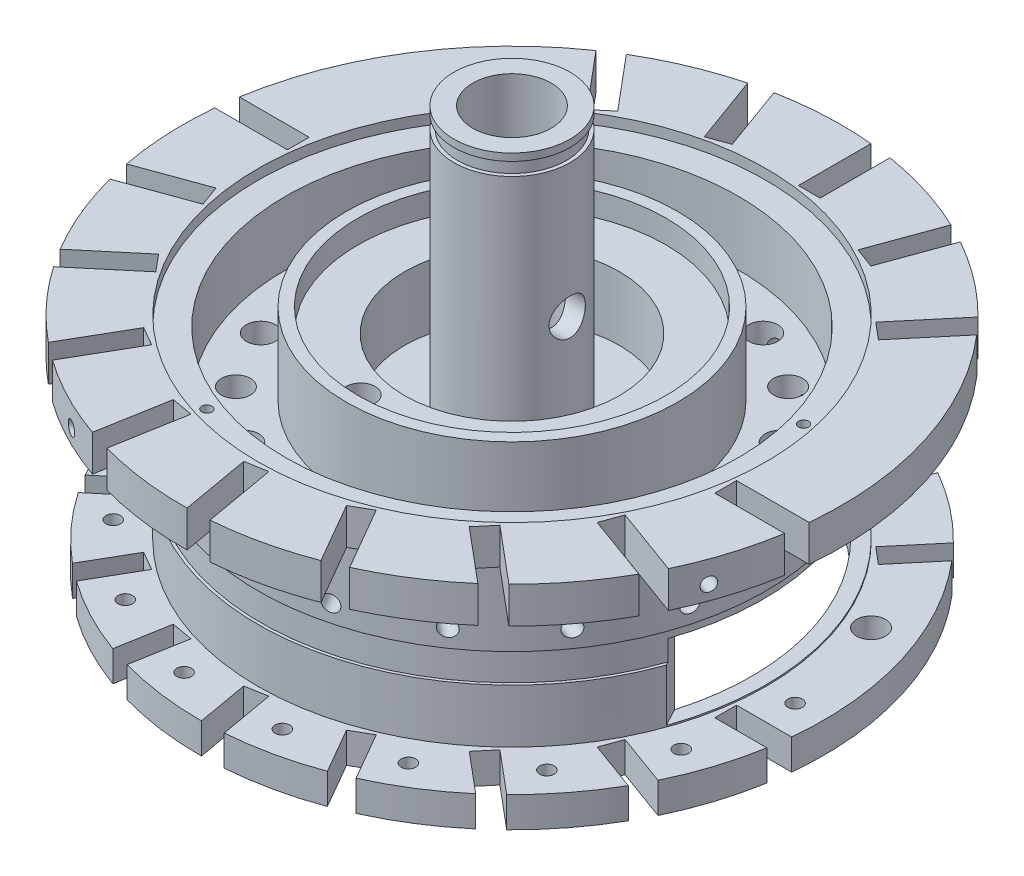
SolidWorks part; units mm, degrees
note: The reader was unsure of these and kept them because the rebuilt part matched: shared geometry of "Sketch13<3>".
ref_plane "Front Plane" through (0, 0, 0) normal (0, 0, 1) x (1, 0, 0)
ref_plane "Top Plane" through (0, 0, 0) normal (0, 1, 0) x (1, 0, 0)
ref_plane "Right Plane" through (0, 0, 0) normal (1, 0, 0) x (0, 0, -1)
sketch "Sketch1" plane through (0, 0, 0) normal (0, 1, 0) x (1, 0, 0)
  circle A0 centre (0, 0) radius 21.5
  dimension "D1" = 43
extrude "Boss-Extrude1" add sketch "Sketch1" along normal blind 2.1
sketch "Sketch2" plane through (0, 2.1, 0) normal (0, 1, 0) x (1, 0, 0)
  circle A0 centre (0, 0) radius 17.5
  dimension "D1" = 35
extrude "Boss-Extrude2" add sketch "Sketch2" along normal blind 10.9
sketch "Sketch3" plane through (0, 13, 0) normal (0, 1, 0) x (1, 0, 0)
  circle A0 centre (0, 0) radius 22.7
  dimension "D1" = 45.4
extrude "Boss-Extrude3" add sketch "Sketch3" along normal blind 2.5
sketch "Sketch4" plane through (0, 0, 0) normal (0, 0, 1) x (1, 0, 0)
  line L0 (0, 0) -> (0, 15.5) construction
  line L1 (22.7, 15.5) -> (-22.7, 15.5) construction
  line L2 (-16.5, 7.6) -> (-16.5, 0)
  line L3 (-21.5, 0) -> (21.5, 0) construction
  line L4 (-16.5, 7.6) -> (-6.5, 7.6)
  line L5 (-6.5, 7.6) -> (-6.5, 7.4)
  line L6 (-6.5, 7.4) -> (-4.5, 7.4)
  line L7 (-4.5, 7.4) -> (-4.5, 8.4)
  line L8 (-4.5, 8.4) -> (0, 8.4)
  line L9 (0, 8.4) -> (0, 0)
  line L10 (0, 0) -> (-16.5, 0)
  dimension "D1" = 33
  dimension "D2" = 9
  dimension "D3" = 7.4
  dimension "D4" = 13
  dimension "D5" = 0.2
  dimension "D6" = 1
revolve "Cut-Revolve1" cut sketch "Sketch4" angle 360 about L0
sketch "Sketch5" plane through (0, 15.5, 0) normal (0, 1, 0) x (1, 0, 0)
  circle A0 centre (0, 0) radius 11.4
  dimension "D1" = 22.8
extrude "Boss-Extrude4" add sketch "Sketch5" along normal blind 0.5
sketch "Sketch6" plane through (0, 16, 0) normal (0, 1, 0) x (1, 0, 0)
  circle A0 centre (0, 0) radius 4
  dimension "D1" = 8
extrude "Boss-Extrude5" add sketch "Sketch6" along normal offset from surface (12 mm away) 20.6 up to face at (0, 7.4, -6.5)
sketch "Sketch7" plane through (0, 0, 0) normal (0, 0, 1) x (1, 0, 0)
  line L0 (0, 28) -> (0, 0) construction
  line L1 (4, 28) -> (-4, 28) construction
  line L2 (17.5, 16) -> (17.5, 14.8)
  line L4 (17.5, 14.8) -> (15.6, 14.8)
  line L5 (15.6, 14.8) -> (15.6, 10.4)
  line L6 (15.6, 10.4) -> (11.4, 10.4)
  line L7 (11.4, 10.4) -> (11.4, 16)
  line L9 (11.4, 16) -> (-11.4, 16) construction
  line L10 (11.4, 16) -> (17.5, 16)
  dimension "D1" = 5.6
  dimension "D2" = 4.4
  dimension "D3" = 35
  dimension "D4" = 31.2
  dimension "D5" = 22.8
revolve "Cut-Revolve2" cut sketch "Sketch7" angle 360 about L0
sketch "Sketch9" plane through (0, 0, 0) normal (0, 0, 1) x (1, 0, 0)
  line L0 (0, 0) -> (0, 28) construction
  line L1 (4, 28) -> (-4, 28) construction
  line L2 (-10.6, 16) -> (-10.6, 14.4)
  line L3 (11.4, 16) -> (-11.4, 16) construction
  line L4 (-10.6, 14.4) -> (-7.4, 14.4)
  line L5 (-7.4, 14.4) -> (-7.4, 10)
  line L6 (-7.4, 10) -> (-4, 10)
  line L7 (-4, 10) -> (-4, 16)
  line L8 (-4, 28) -> (-4, 16) construction
  line L9 (-10.6, 16) -> (-4, 16)
  dimension "D1" = 21.2
  dimension "D2" = 1.6
  dimension "D3" = 6
  dimension "D4" = 14.8
revolve "Cut-Revolve3" cut sketch "Sketch9" angle 360 about L0
sketch "Sketch10" plane through (0, 0, 0) normal (0, 0, 1) x (1, 0, 0)
  line L0 (0, 28) -> (0, 0) construction
  line L1 (4, 28) -> (-4, 28) construction
  line L2 (4, 10) -> (4, 28) construction
  line L3 (4, 27.5) -> (3.75, 27.5)
  line L4 (4, 27.5) -> (4, 26.6)
  line L5 (4, 26.6) -> (3.75, 26.6)
  line L6 (3.75, 27.5) -> (3.75, 26.6)
  line L7 (11.4, 16) -> (-11.4, 16) construction
  dimension "D1" = 0.9
  dimension "D2" = 11.5
  dimension "D3" = 7.5
revolve "Cut-Revolve4" cut sketch "Sketch10" angle 360 about L0
sketch "Sketch11" plane through (0, 0, 0) normal (0, 0, 1) x (1, 0, 0)
  line L0 (0, 0) -> (0, 28) construction
  line L1 (4, 28) -> (-4, 28) construction
  line L2 (17.5, 2.1) -> (17.5, 13) construction
  line L3 (17.5, 7.8) -> (17.3, 7.8)
  line L4 (17.5, 7.8) -> (17.5, 5.8)
  line L5 (17.5, 5.8) -> (17.3, 5.8)
  line L6 (17.3, 7.8) -> (17.3, 5.8)
  line L7 (-21.5, 0) -> (21.5, 0) construction
  dimension "D1" = 5.8
  dimension "D2" = 2
  dimension "D3" = 34.6
revolve "Cut-Revolve5" cut sketch "Sketch11" angle 360 about L0
sketch "Sketch12" plane through (0, 0, 0) normal (0, 0, 1) x (1, 0, 0)
  line L0 (0, 28) -> (0, 0) construction
  line L1 (4, 28) -> (-4, 28) construction
  line L2 (-4.5, 8.4) -> (4.5, 8.4) construction
  line L3 (0, 28) -> (2.7, 28)
  line L4 (0, 28) -> (0, 8.4)
  line L6 (2.7, 28) -> (2.7, 23)
  line L7 (2.7, 23) -> (2.75, 23)
  line L9 (2.7, 13) -> (2.75, 13)
  line L10 (2.75, 23) -> (2.75, 13)
  line L12 (0, 8.4) -> (2.7, 8.4)
  line L13 (2.7, 13) -> (2.7, 8.4)
  dimension "D1" = 5.4
  dimension "D2" = 5.5
  dimension "D3" = 5
  dimension "D4" = 10
revolve "Cut-Revolve6" cut sketch "Sketch12" angle 360 about L0
ref_plane "Plane1" through (0, 2.2, 0) normal (0, 1, 0) x (1, 0, 0)
sketch "Sketch13" plane through (0, 2.2, 0) normal (0, 1, 0) x (1, 0, 0)
  line L0 (0, 0) -> (35.2335, 0) construction
  line L1 (0, 0) -> (61.7298, 16.5405) construction
  line L2 (-0.5176, 1.9319) -> (60.305, 18.2292) construction
  line L3 (-0.5176, 1.9319) -> (37.0796, 12.006) construction
  line L4 (0, 0) -> (1.4239, 40.7745) construction
  line L5 (-1.9988, 0.0698) -> (0.1874, 62.6729) construction
  line L6 (-1.9988, 0.0698) -> (-0.5749, 40.8443) construction
  line L7 (0, 0) -> (37.5972, 10.0741) construction
  circle A0 centre (0, 0) radius 13 construction
  circle A2 centre (60.305, 18.2292) radius 50
  circle A3 centre (0.1988, 62.9997) radius 50
  circle A4 centre (0, 0) radius 15.6 construction
  point P19 (10.7925, 11.2642)
  dimension "D3" = 26
  dimension "D4" = 100
  dimension "D1" = 15
  dimension "D5" = 73
  dimension "D2" = 2
  dimension "D6" = 2
extrude "Cut-Extrude1" cut sketch "Sketch13" along normal blind 5 contours A2
extrude "Cut-Extrude2" cut sketch "Sketch13<3>" along normal blind 5 contours A3
sketch "Sketch13<3>" plane through (0, 2.2, 0) normal (0, 1, 0) x (1, 0, 0) same geometry as "Sketch13"
sketch "Sketch14" plane through (0, 15.5, 0) normal (0, 1, 0) x (1, 0, 0)
  line L0 (0, 0) -> (22.7, 0) construction
  line L2 (17.6, -2.13) -> (22.5998, -2.13)
  line L3 (17.6, -2.13) -> (17.6, -3.63)
  line L4 (17.6, -3.63) -> (22.4079, -3.63)
  circle A0 centre (0, 0) radius 22.7 construction
  arc A1 (22.4079, -3.63) -> (22.5998, -2.13) centre (0, 0) ccw
  dimension "D1" = 17.6
  dimension "D2" = 1.5
  dimension "D3" = 2.13
extrude "Cut-Extrude3" cut sketch "Sketch14" against normal through all
pattern_circular "CirPattern1" count 10 every 20 about axis through (0, 0, 0) along (0, 1, 0) of "Cut-Extrude3"
sketch "Sketch17" plane through (0, 15.5, 0) normal (0, 1, 0) x (1, 0, 0)
  line L0 (16.1586, 15.9433) -> (12.9447, 12.1132)
  line L1 (14.0938, 11.1491) -> (17.1842, 14.8321)
  line L2 (12.9447, 12.1132) -> (14.0938, 11.1491)
  line L3 (22.5998, -2.13) -> (17.6, -2.13)
  line L4 (17.6, -3.63) -> (22.4079, -3.63)
  line L5 (17.6, -2.13) -> (17.6, -3.63)
  line L6 (22.5998, -2.13) -> (17.6, -2.13) construction
  line L7 (17.6, -3.63) -> (22.4079, -3.63) construction
  line L8 (17.6, -2.13) -> (17.6, -3.63) construction
  line L9 (0, 0) -> (17.6, -2.13) construction
  line L10 (0, 0) -> (12.9447, 12.1132) construction
  arc A0 (17.1842, 14.8321) -> (16.1586, 15.9433) centre (0, 0) ccw
  arc A1 (22.4079, -3.63) -> (22.5998, -2.13) centre (0, 0) ccw
  arc A2 (22.4079, -3.63) -> (22.5998, -2.13) centre (0, 0) ccw construction
  dimension "D3" = 50
  dimension "D1" = 0
  dimension "D2" = 2
extrude "Cut-Extrude4" cut sketch "Sketch17" against normal through all
pattern_circular "CirPattern2" count 5 every 20 about axis through (0, 0, 0) along (0, 1, 0) of "Cut-Extrude4"
sketch "Sketch15" plane through (0, 15.5, 0) normal (0, 1, 0) x (1, 0, 0)
  line L0 (0, 0) -> (0, -23.2727) construction
  line L1 (0, 0) -> (-24.3784, 0) construction
  line L2 (0, 0) -> (0, 26.6323) construction
sketch "Sketch18" plane through (0, 10.4, 0) normal (0, 1, 0) x (1, 0, 0)
  line L0 (0, 0) -> (22.7, 0) construction
  arc A0 (22.5998, -2.13) -> (17.1842, 14.8321) centre (0, 0) ccw construction
hole_wizard "Ø2.0 (2) Diameter Hole1" positions "Sketch20" profile "Sketch19" hole size "Ø2.0" standard "DIN" end condition up to next
sketch "Sketch20" plane through (0, 14.4, 0) normal (0, 1, 0) x (1, 0, 0)
  line L0 (0, 0) -> (22.7, 0) construction
  line L1 (0, 0) -> (12.6859, -4.6173) construction
  line L2 (0, 0) -> (10.3416, -8.6776) construction
  line L3 (0, 0) -> (6.75, -11.6913) construction
  line L4 (0, 0) -> (2.3443, -13.2949) construction
  line L5 (0, 0) -> (-2.3443, -13.2949) construction
  line L6 (0, 0) -> (-6.75, -11.6913) construction
  line L7 (-10.3416, -8.6776) -> (0, 0) construction
  line L8 (0, 0) -> (-12.6859, -4.6173) construction
  line L9 (-13.5, 0) -> (0, 0) construction
  line L10 (0, 0) -> (-12.6859, 4.6173) construction
  line L11 (0, 0) -> (11.6913, 6.75) construction
  line L12 (8.6776, 10.3416) -> (0, 0) construction
  line L13 (4.6173, 12.6859) -> (0, 0) construction
  line L14 (0, 0) -> (0, 13.5) construction
  line L15 (-4.6173, 12.6859) -> (0, 0) construction
  line L16 (0, 0) -> (-8.6776, 10.3416) construction
  circle A0 centre (0, 0) radius 13.5 construction
  point P0 (13.5, 0)
  point P13 (12.6859, -4.6173)
  point P17 (10.3416, -8.6776)
  point P19 (6.75, -11.6913)
  point P23 (2.3443, -13.2949)
  point P26 (-2.3443, -13.2949)
  point P28 (-6.75, -11.6913)
  point P29 (-10.3416, -8.6776)
  point P33 (-12.6859, -4.6173)
  point P34 (-13.5, 0)
  point P38 (-12.6859, 4.6173)
  point P79 (-8.6776, 10.3416)
  point P82 (-4.6173, 12.6859)
  point P85 (0, 13.5)
  point P88 (4.6173, 12.6859)
  point P91 (8.6776, 10.3416)
  point P94 (11.6913, 6.75)
  dimension "D1" = 27
  dimension "D2" = 20
  dimension "D3" = 20
  dimension "D4" = 20
  dimension "D5" = 20
  dimension "D6" = 20
  dimension "D7" = 20
  dimension "D8" = 20
  dimension "D9" = 20
  dimension "D10" = 20
  dimension "D11" = 20
  dimension "D12" = 30
  dimension "D13" = 50
  dimension "D14" = 70
  dimension "D15" = 110
  dimension "D16" = 130
sketch "Sketch19" plane through (13.5, 14.4, 0) normal (1, 0, 0) x (0, 0, 1)
  line L0 (0, 0) -> (0, 6.8)
  line L1 (0, 6.8) -> (1, 6.8)
  line L2 (1, 6.8) -> (1, 0)
  line L5 (1, 0) -> (0, 0)
  line L11 (0, -6.35) -> (0, 107.95) construction
  dimension "Thru Hole Dia." = 2
  dimension "Thru Hole Depth" = 6.8
hole_wizard "Ø2.0 (2) Diameter Hole2" positions "Sketch23" profile "Sketch22" hole size "Ø2.0" standard "DIN" end condition up to next
sketch "Sketch23" plane through (0, 14.4, 0) normal (0, 1, 0) x (1, 0, 0)
  line L0 (0, 0) -> (0, -9) construction
  line L1 (0, 0) -> (-2.3443, -13.2949) construction
  line L2 (0, 0) -> (-8.6776, 10.3416) construction
  circle A0 centre (0, 0) radius 9 construction
  point P18 (-1.5628, -8.8633)
  point P20 (-5.7851, 6.8944)
  dimension "D1" = 18
sketch "Sketch22" plane through (-1.5628, 14.4, 8.8633) normal (1, 0, 0) x (0, 0, 1)
  line L0 (0, 0) -> (0, 6.8)
  line L1 (0, 6.8) -> (1, 6.8)
  line L2 (1, 6.8) -> (1, 0)
  line L5 (1, 0) -> (0, 0)
  line L11 (0, -6.35) -> (0, 107.95) construction
  dimension "Thru Hole Dia." = 2
  dimension "Thru Hole Depth" = 6.8
sketch "Sketch24" plane through (0, 7.6, 0) normal (0, -1, 0) x (1, 0, 0)
  circle A0 centre (-8.6776, -10.3416) radius 2
  dimension "D1" = 4
extrude "Cut-Extrude6" cut sketch "Sketch24" against normal offset from surface (0.3 mm away) 2.5 up to face at (13.5, 10.4, 1)
hole_wizard "M1 Tapped Hole1" positions "Sketch26" profile "Sketch25" tap size "M1.2x0.25" standard "ANSI Metric"
sketch "Sketch26" plane through (0, 14.8, 0) normal (0, 1, 0) x (1, 0, 0)
  line L0 (0, 0) -> (22.7, 0) construction
  line L1 (0, 0) -> (15.8412, 4.2446) construction
  line L2 (0, 0) -> (-5.6091, -15.411) construction
  line L3 (0, 0) -> (-13.4341, 9.4067) construction
  arc A0 (22.5998, -2.13) -> (17.1842, 14.8321) centre (0, 0) ccw construction
  circle A1 centre (0, 0) radius 16.4 construction
  point P0 (15.8412, 4.2446)
  point P20 (-5.6091, -15.411)
  point P24 (-13.4341, 9.4067)
  dimension "D1" = 32.8
  dimension "D2" = 15
  dimension "D3" = 125
  dimension "D4" = 230
cosmetic thread "Hole Thread1" parameters "D1"=3, "D2"=1.2
cosmetic thread "Hole Thread2" parameters "D1"=3, "D2"=1.2
cosmetic thread "Hole Thread3" parameters "D1"=3, "D2"=1.2
sketch "Sketch25" plane through (15.8412, 14.8, -4.2446) normal (1, 0, 0) x (0, 0, 1)
  line L0 (0, 0) -> (0, 5.2103)
  line L1 (0, 5.2103) -> (0.35, 5)
  line L2 (0.35, 5) -> (0.35, 0)
  line L5 (0.35, 0) -> (0, 0)
  line L10 (0, 5.2103) -> (-0.35, 5) construction
  line L11 (0, -6.35) -> (0, 107.95) construction
  dimension "Tap Drill Dia." = 0.7
  dimension "Tap Drill Depth" = 5
  dimension "Drill Angle" = 118
hole_wizard "Ø2.0 (2) Diameter Hole3" positions "Sketch30" profile "Sketch29" hole size "Ø2.0" standard "DIN"
sketch "Sketch30" plane through (0, 2.1, 0) normal (0, 1, 0) x (1, 0, 0)
  line L0 (0, 0) -> (19, 0) construction
  line L1 (0, 0) -> (17.6165, 7.1175) construction
  line L2 (0, 0) -> (-12.7135, 14.1198) construction
  line L3 (0, 0) -> (-17.6165, -7.1175) construction
  line L4 (0, 0) -> (5.8713, 18.0701) construction
  circle A0 centre (0, 0) radius 19 construction
  point P8 (17.6165, 7.1175)
  point P11 (-12.7135, 14.1198)
  point P14 (-17.6165, -7.1175)
  point P18 (5.8713, 18.0701)
  dimension "D1" = 38
  dimension "D2" = 22
  dimension "D3" = 132
  dimension "D4" = 202
  dimension "D5" = 72
sketch "Sketch29" plane through (17.6165, 2.1, -7.1175) normal (1, 0, 0) x (0, 0, 1)
  line L0 (0, 0) -> (0, 2.1)
  line L1 (0, 2.1) -> (1, 2.1)
  line L2 (1, 2.1) -> (1, 0)
  line L5 (1, 0) -> (0, 0)
  line L11 (0, -6.35) -> (0, 107.95) construction
  dimension "Thru Hole Dia." = 2
  dimension "Thru Hole Depth" = 2.1
hole_wizard "Ø1.0 (1) Diameter Hole1" positions "Sketch32" profile "Sketch31" hole size "Ø1.0" standard "DIN"
sketch "Sketch32" plane through (0, 2.1, 0) normal (0, 1, 0) x (1, 0, 0)
  line L0 (0, 0) -> (18.0801, 7.3048) construction
  line L1 (0, 0) -> (19.5, 0) construction
  line L2 (0, 0) -> (18.324, -6.6694) construction
  line L3 (0, 0) -> (14.9379, -12.5344) construction
  line L4 (0, 0) -> (9.75, -16.8875) construction
  line L5 (0, 0) -> (3.3861, -19.2038) construction
  line L6 (0, 0) -> (-3.3861, -19.2038) construction
  line L7 (-9.75, -16.8875) -> (0, 0) construction
  line L8 (-14.9379, -12.5344) -> (0, 0) construction
  circle A0 centre (0, 0) radius 19.5 construction
  point P14 (18.324, -6.6694)
  point P19 (9.75, -16.8875)
  point P21 (3.3861, -19.2038)
  point P24 (-3.3861, -19.2038)
  point P25 (-9.75, -16.8875)
  point P27 (-14.9379, -12.5344)
  point P45 (14.9379, -12.5344)
  point P46 (19.5, 0)
  dimension "D1" = 20
  dimension "D8" = 39
  dimension "D2" = 20
  dimension "D3" = 20
  dimension "D4" = 20
  dimension "D5" = 20
  dimension "D6" = 20
  dimension "D7" = 20
sketch "Sketch31" plane through (18.324, 2.1, 6.6694) normal (1, 0, 0) x (0, 0, 1)
  line L0 (0, 0) -> (0, 2.1)
  line L1 (0, 2.1) -> (0.5, 2.1)
  line L2 (0.5, 2.1) -> (0.5, 0)
  line L5 (0.5, 0) -> (0, 0)
  line L11 (0, -6.35) -> (0, 107.95) construction
  dimension "Thru Hole Dia." = 1
  dimension "Thru Hole Depth" = 2.1
sketch "Sketch33" plane through (0, 15.5, 0) normal (0, 1, 0) x (1, 0, 0)
  line L0 (0, 0) -> (22.7, 0) construction
  line L1 (0, 0) -> (21.331, -7.7639) construction
  line L2 (0, 0) -> (-9.951, -20.4026) construction
  line L3 (0, 0) -> (-21.331, 7.7639) construction
  arc A0 (22.5998, -2.13) -> (17.1842, 14.8321) centre (0, 0) ccw construction
  arc A1 (20.5084, -9.7311) -> (22.4079, -3.63) centre (0, 0) ccw construction
  arc A2 (-6.0221, -21.8866) -> (0.3162, -22.6978) centre (0, 0) ccw construction
  arc A3 (-12.8952, 18.6816) -> (-22.4079, 3.63) centre (0, 0) ccw construction
  dimension "D1" = 20
  dimension "D2" = 116
  dimension "D3" = 200
ref_plane "Plane2" through (21.331, 15.5, 7.7639) normal (0.9397, 0, 0.342) x (0.342, 0, -0.9397)
hole_wizard "M1.2x0.25 Tapped Hole2" positions "Sketch35" profile "Sketch36" tap size "M1.2x0.25" standard "ANSI Metric"
sketch "Sketch35" plane through (21.331, 15.5, 7.7639) normal (0.9397, 0, 0.342) x (0.342, 0, -0.9397)
  line L0 (0, 0) -> (0, -2.5201) construction
  line L1 (11.4, 0.5) -> (-11.4, 0.5) construction
  point P0 (0, -1.5)
  dimension "D1" = 2
sketch "Sketch36" plane through (21.331, 14, 7.7639) normal (0, 1, 0) x (0.342, 0, -0.9397)
  line L0 (0, 0) -> (0, 4.7854)
  line L1 (0, 4.7854) -> (0.475, 4.5)
  line L2 (0.475, 4.5) -> (0.475, 0)
  line L5 (0.475, 0) -> (0, 0)
  line L10 (0, 4.7854) -> (-0.475, 4.5) construction
  line L11 (0, -6.35) -> (0, 107.95) construction
  dimension "Tap Drill Dia." = 0.95
  dimension "Tap Drill Depth" = 4.5
  dimension "Drill Angle" = 118
cosmetic thread "Hole Thread4" parameters "D1"=3, "D2"=1.2
ref_plane "Plane3" through (-9.951, 15.5, 20.4026) normal (-0.4384, 0, 0.8988) x (0.8988, 0, 0.4384)
hole_wizard "M1.2x0.25 Tapped Hole3" positions "Sketch38" profile "Sketch37" tap size "M1.2x0.25" standard "ANSI Metric"
sketch "Sketch38" plane through (-9.951, 15.5, 20.4026) normal (-0.4384, 0, 0.8988) x (0.8988, 0, 0.4384)
  line L0 (0, 0) -> (0, -2.5) construction
  line L1 (0, 0) -> (22.5756, 0) construction
  line L2 (0, 0) -> (20.4026, 0) construction
  line L3 (-3.7013, -2.5) -> (2.6871, -2.5) construction
  line L4 (11.4, 0.5) -> (-11.4, 0.5) construction
  point P0 (0, -1.5)
  dimension "D1" = 2
sketch "Sketch37" plane through (-9.951, 14, 20.4026) normal (0, 1, 0) x (0.8988, 0, 0.4384)
  line L0 (0, 0) -> (0, 4.7854)
  line L1 (0, 4.7854) -> (0.475, 4.5)
  line L2 (0.475, 4.5) -> (0.475, 0)
  line L5 (0.475, 0) -> (0, 0)
  line L10 (0, 4.7854) -> (-0.475, 4.5) construction
  line L11 (0, -6.35) -> (0, 107.95) construction
  dimension "Tap Drill Dia." = 0.95
  dimension "Tap Drill Depth" = 4.5
  dimension "Drill Angle" = 118
cosmetic thread "Hole Thread5" parameters "D1"=3, "D2"=1.2
ref_plane "Plane7" through (-21.331, 15.5, -7.7639) normal (-0.9397, 0, -0.342) x (-0.342, 0, 0.9397)
hole_wizard "M1.2x0.25 Tapped Hole4" positions "Sketch46" profile "Sketch45" tap size "M1.2x0.25" standard "AS"
sketch "Sketch46" plane through (-21.331, 15.5, -7.7639) normal (-0.9397, 0, -0.342) x (-0.342, 0, 0.9397)
  line L2 (0, 0) -> (22.5756, 0) construction
  line L3 (0, 0) -> (0, -1.5) construction
  line L4 (0, 0) -> (-7.7639, 0) construction
  line L5 (11.4, 0.5) -> (-11.4, 0.5) construction
  point P0 (0, -1.5)
  dimension "D1" = 2
cosmetic thread "Hole Thread8" parameters "D1"=3, "D2"=1.2
sketch "Sketch45" plane through (-21.331, 14, -7.7639) normal (0, 1, 0) x (-0.342, 0, 0.9397)
  line L0 (0, 0) -> (0, 4.7854)
  line L1 (0, 4.7854) -> (0.475, 4.5)
  line L2 (0.475, 4.5) -> (0.475, 0)
  line L5 (0.475, 0) -> (0, 0)
  line L10 (0, 4.7854) -> (-0.475, 4.5) construction
  line L11 (0, -6.35) -> (0, 107.95) construction
  dimension "Tap Drill Dia." = 0.95
  dimension "Tap Drill Depth" = 4.5
  dimension "Drill Angle" = 118
ref_plane "Plane4" through (0, 9, 0) normal (0, 1, 0) x (1, 0, 0)
sketch "Sketch39" plane through (0, 9, 0) normal (0, 1, 0) x (1, 0, 0)
  line L0 (12.6859, -4.6173) -> (17.6, -4.6173) construction
  line L1 (17.6, -2.13) -> (17.6, -3.63) construction
  line L2 (11.6913, 6.75) -> (14.8501, 10.5145) construction
  line L3 (0, 0) -> (12.6859, -4.6173) construction
  line L4 (0, 0) -> (11.6913, 6.75) construction
  dimension "D1" = 2
  dimension "D2" = 50
ref_plane "Plane5" through (17.6, 9, 4.6173) normal (1, 0, 0) x (0, 0, -1)
hole_wizard "M1.4x0.3 Tapped Hole1" positions "Sketch41" profile "Sketch40" tap size "M1.4x0.3" standard "ANSI Metric"
sketch "Sketch41" plane through (17.6, 9, 4.6173) normal (1, 0, 0) x (0, 0, -1)
  point P0 (0, 0)
sketch "Sketch40" plane through (17.6, 9, 4.6173) normal (0, 1, 0) x (0, 0, -1)
  line L0 (0, 0) -> (0, 29.2859)
  line L1 (0, 29.2859) -> (0.55, 29.2859)
  line L2 (0.55, 29.2859) -> (0.55, 0)
  line L5 (0.55, 0) -> (0, 0)
  line L11 (0, -6.35) -> (0, 107.95) construction
  dimension "Thru Tap Drill Dia." = 1.1
  dimension "Thru Tap Drill Depth" = 29.2859
cosmetic thread "Hole Thread6" parameters "D1"=2.8, "D2"=1.4
pattern_circular "CirPattern3" count 10 every 20 about axis through (0, 59.9137, 0) along (0, -1, 0) of "M1.4x0.3 Tapped Hole1"
hole_wizard "M1.4x0.3 Tapped Hole2" positions "Sketch43" profile "Sketch42" tap size "M1.4x0.3" standard "ANSI Metric"
sketch "Sketch43" plane through (11.3131, 0, -13.4824) normal (0.6428, 0, -0.766) x (-0.766, 0, -0.6428)
  point P0 (-4.6173, 9)
sketch "Sketch42" plane through (14.8501, 9, -10.5145) normal (0, 1, 0) x (-0.766, 0, -0.6428)
  line L0 (0, 0) -> (0, 24.4011)
  line L1 (0, 24.4011) -> (0.55, 24.4011)
  line L2 (0.55, 24.4011) -> (0.55, 0)
  line L5 (0.55, 0) -> (0, 0)
  line L11 (0, -6.35) -> (0, 107.95) construction
  dimension "Thru Tap Drill Dia." = 1.1
  dimension "Thru Tap Drill Depth" = 24.4011
cosmetic thread "Hole Thread7" parameters "D1"=2.8, "D2"=1.4
pattern_circular "CirPattern4" count 5 every 20 about axis through (0, 59.9137, 0) along (0, -1, 0) of "M1.4x0.3 Tapped Hole2"
ref_plane "Plane6" through (0, 17.4, 0) normal (0, -1, 0) x (-1, 0, 0)
sketch "Sketch44" plane through (0, 17.4, 0) normal (0, -1, 0) x (-1, 0, 0)
  line L0 (0, 0) -> (-4.9962, 0) construction
  line L2 (-2.3932, 1.25) -> (-4, 1.25)
  line L3 (-2.3932, 1.25) -> (-2.3932, 0)
  line L4 (-2.3932, 0) -> (-4, 0)
  line L5 (-4, 1.25) -> (-4, 0)
  circle A0 centre (0, 0) radius 2.7 construction
  circle A1 centre (0, 0) radius 4 construction
  dimension "D1" = 2.5
revolve "Cut-Revolve7" cut sketch "Sketch44" angle 360 about L0
